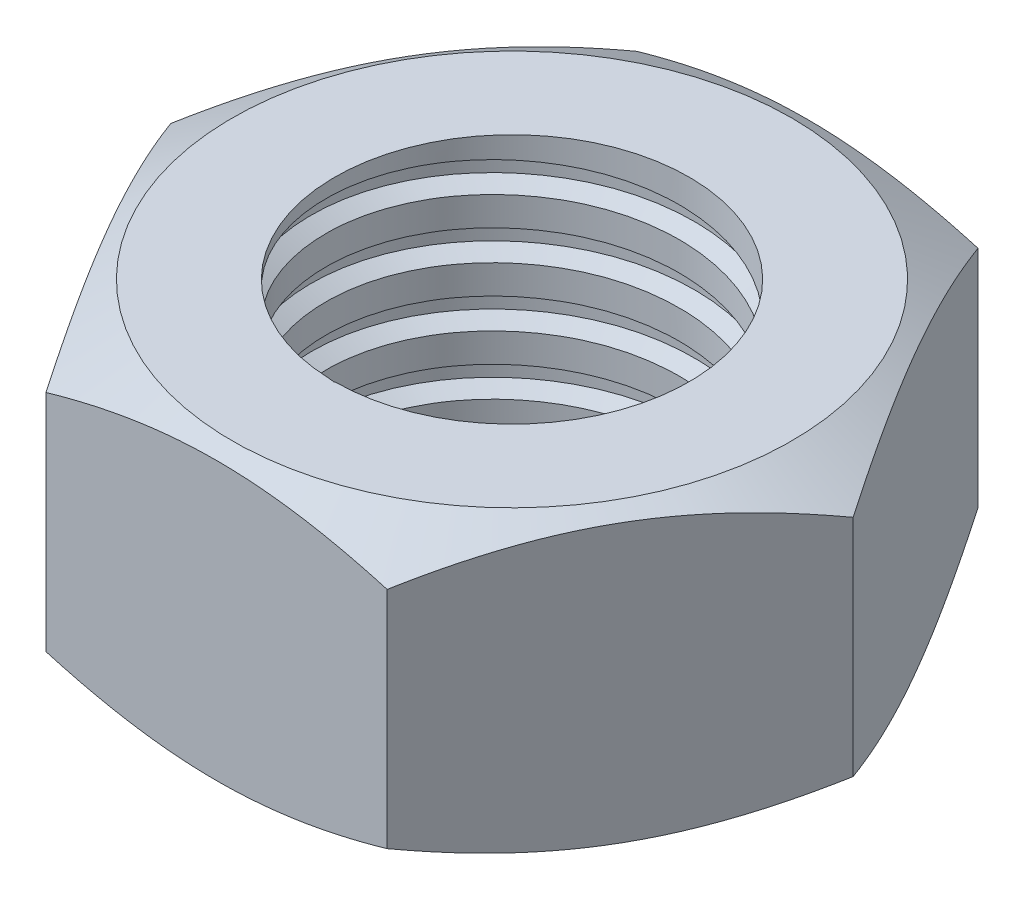
SolidWorks part; units mm, degrees
ref_plane "前基準面" through (0, 0, 0) normal (0, 0, 1) x (1, 0, 0)
ref_plane "上基準面" through (0, 0, 0) normal (0, 1, 0) x (1, 0, 0)
ref_plane "右基準面" through (0, 0, 0) normal (1, 0, 0) x (0, 0, -1)
sketch "草圖2" plane through (0, 0, 0) normal (0, 1, 0) x (1, 0, 0)
  line L1 (2.8868, 0) -> (1.4434, 2.5)
  line L2 (1.4434, 2.5) -> (-1.4434, 2.5)
  line L3 (-1.4434, 2.5) -> (-2.8868, 0)
  line L4 (-2.8868, 0) -> (-1.4434, -2.5)
  line L5 (-1.4434, -2.5) -> (1.4434, -2.5)
  line L6 (1.4434, -2.5) -> (2.8868, 0)
  circle A0 centre (0, 0) radius 2.5 construction
  dimension "D1" = 5
extrude "填料-伸長1" add sketch "草圖2" along normal blind 2.5
sketch "草圖3" plane through (0, 2.5, 0) normal (0, 1, 0) x (1, 0, 0)
  circle A0 centre (0, 0) radius 1.5
  dimension "D1" = 3
extrude "除料-伸長1" cut sketch "草圖3" against normal through all
sketch "草圖4" plane through (0, 0, 0) normal (0, 0, 1) x (1, 0, 0)
  line L0 (0, 0) -> (0, 3.5173) construction
  line L1 (2.8868, 1.25) -> (-3.5574, 1.25) construction
  line L2 (2.8868, 2.5) -> (2.8868, 0) construction
  line L3 (2.3671, 2.5) -> (2.8868, 2.2)
  line L4 (1.4434, 2.5) -> (2.8868, 2.5) construction
  line L5 (2.8868, 2.2) -> (2.8868, 2.5)
  line L6 (2.8868, 2.5) -> (2.3671, 2.5)
  line L7 (2.8868, 0) -> (2.3671, 0)
  line L8 (2.8868, 0.3) -> (2.8868, 0)
  line L9 (2.3671, 0) -> (2.8868, 0.3)
  dimension "D1" = 30
  dimension "D2" = 0.3
revolve "除料-旋轉1" cut sketch "草圖4" angle 360 about L0
sketch "草圖5" plane through (0, 0, 0) normal (0, -1, 0) x (1, 0, 0)
  circle A0 centre (0, 0) radius 1.5 construction
  circle A1 centre (0, 0) radius 1.5
curve "螺旋曲線/渦捲線1" pitch 0.5 height 2.375 radius 1.5 centre (0, 0, 0) axis (0, 1, 0) start towards (1, 0, 0)
sketch "草圖6" plane through (0, 0, 0) normal (0, 0, 1) x (1, 0, 0)
  line L2 (1.625, 0.0557) -> (1.625, -0.0557)
  line L5 (1.375, 0) -> (1.5, 0) construction
  line L6 (1.375, -0.2) -> (1.625, -0.0557)
  line L7 (1.375, 0.2) -> (1.625, 0.0557)
  line L8 (1.375, -0.2) -> (1.375, 0.2)
  line L9 (1.5, 0) -> (1.5, 0.1278) construction
  line L10 (1.375, 0) -> (1.6583, 0) construction
  line L11 (-2.3671, 0) -> (2.3671, 0) construction
  point P1 (0, 0)
  point P14 (1.5, 0)
  dimension "D1" = 0.4
  dimension "D2" = 0.25
  dimension "D3" = 0.25
  dimension "D4" = 60
  dimension "D5" = 0.125
sweep "除料-掃出7" cut profiles "草圖6" path "螺旋曲線/渦捲線1" align with end faces yes
